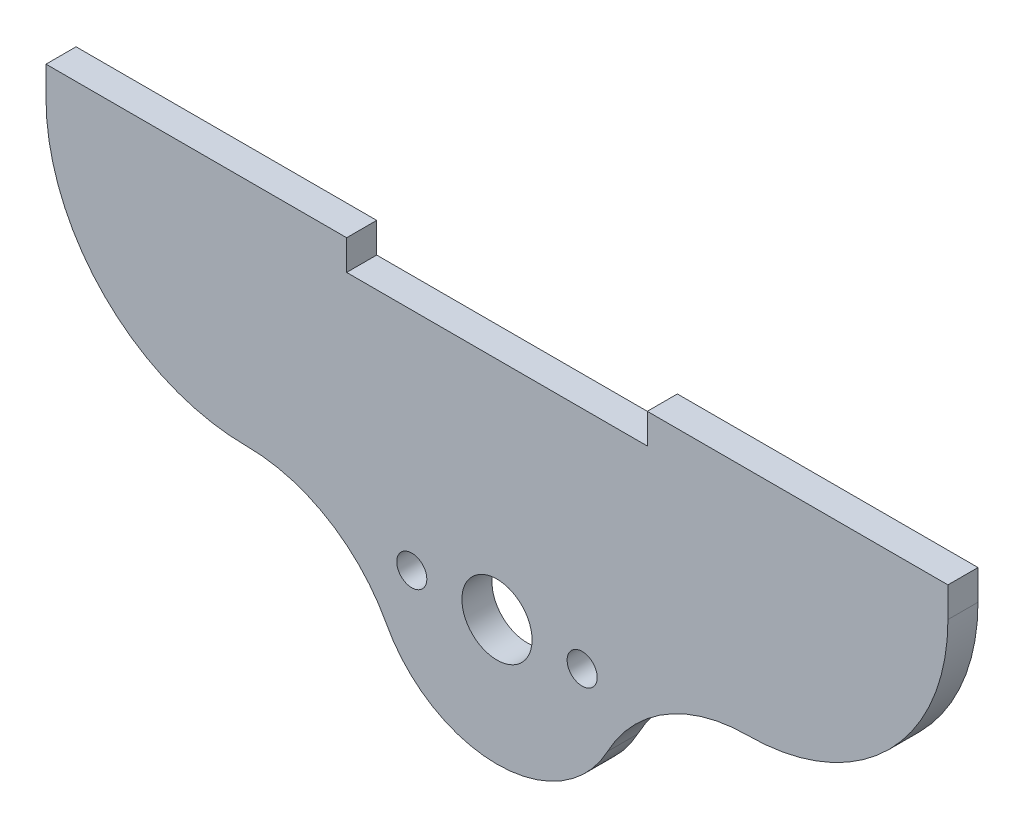
SolidWorks part; units mm, degrees
ref_plane "Front Plane" through (0, 0, 0) normal (0, 0, 1) x (1, 0, 0)
ref_plane "Top Plane" through (0, 0, 0) normal (0, 1, 0) x (1, 0, 0)
ref_plane "Right Plane" through (0, 0, 0) normal (1, 0, 0) x (0, 0, -1)
sketch "Sketch1" plane through (0, 0, 0) normal (0, 0, 1) x (1, 0, 0)
  line L0 (-8.5, 0) -> (8.5, 0) construction
  line L1 (-15, 22.5) -> (15, 22.5)
  line L2 (-45, 22.5) -> (-45, 28.6955) construction
  line L3 (45, 22.5) -> (45, 25.5) construction
  line L4 (-25, 2.5) -> (-49.9345, 2.5) construction
  line L5 (25, 2.5) -> (47.5049, 2.5) construction
  line L8 (-45, 22.5) -> (-45, 25.5)
  line L9 (-45, 25.5) -> (-15, 25.5)
  line L10 (-15, 22.5) -> (-15, 25.5)
  line L12 (45, 22.5) -> (45, 25.5)
  line L13 (45, 25.5) -> (15, 25.5)
  line L14 (15, 22.5) -> (15, 25.5)
  circle A0 centre (-8.5, 0) radius 1.5
  circle A1 centre (8.5, 0) radius 1.5
  circle A2 centre (0, 0) radius 3.5
  circle A3 centre (0, 0) radius 12.5 construction
  arc A4 (-11.0294, -5.8824) -> (11.0294, -5.8824) centre (0, 0) ccw
  arc A5 (-45, 22.5) -> (-25, 2.5) centre (-25, 22.5) ccw
  arc A6 (-11.0294, -5.8824) -> (-25, 2.5) centre (-25, -13.3333) ccw
  arc A7 (11.0294, -5.8824) -> (25, 2.5) centre (25, -13.3333) cw
  arc A8 (25, 2.5) -> (45, 22.5) centre (25, 22.5) ccw
  point P4 (0, 0)
  point P10 (0, 22.5)
  point P12 (0, 12.5)
  dimension "D1" = 3
  dimension "D3" = 7
  dimension "D5" = 25
  dimension "D2" = 17
  dimension "D4" = 90
  dimension "D6" = 10
  dimension "D7" = 20
  dimension "D8" = 3
extrude "Boss-Extrude1" add sketch "Sketch1" along normal blind 3
